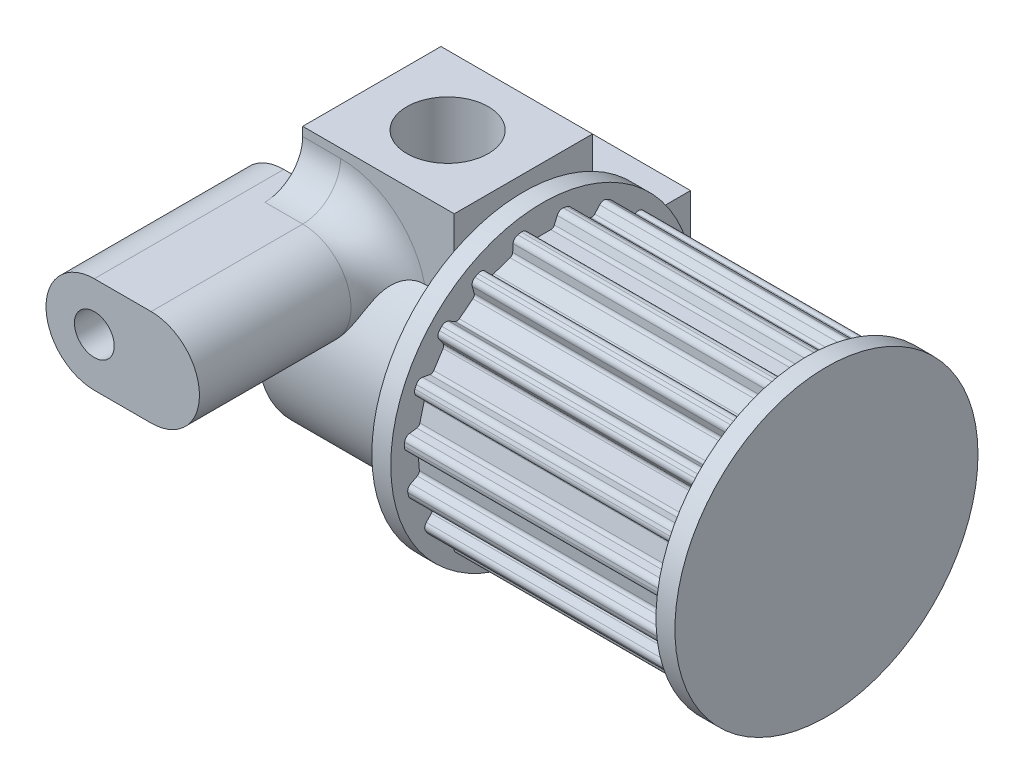
SolidWorks part; units mm, degrees
material "PLA Black"
ref_plane "Front" through (0, 0, 0) normal (0, 0, 1) x (1, 0, 0)
ref_plane "Top" through (0, 0, 0) normal (0, 1, 0) x (1, 0, 0)
ref_plane "Right" through (0, 0, 0) normal (1, 0, 0) x (0, 0, -1)
sketch "Sketch1" plane through (0, 0, 0) normal (1, 0, 0) x (0, 0, -1)
  line L0 (1.118, 1) -> (-1.118, 1) construction
  line L1 (-3.65, 4.8249) -> (3.65, 4.8249)
  line L2 (4.8249, 3.65) -> (4.8249, -3.65)
  line L3 (0, 0) -> (11.6334, 0) construction
  line L4 (0, 0) -> (0, 8.6732) construction
  arc A0 (-1.118, 1) -> (1.118, 1) centre (0, 0) ccw construction
  circle A1 centre (0, 0) radius 1.75
  arc A2 (4.8249, -3.65) -> (-3.65, 4.8249) centre (0, 0) cw
  arc A3 (4.8249, 3.65) -> (3.65, 4.8249) centre (0, 0) ccw
  dimension "D1" = 3
  dimension "D3" = 0.25
  dimension "D5" = 6.05
  dimension "D2" = 1
  dimension "D4" = 7.3
extrude "Boss-Extrude1" add sketch "Sketch1" along normal mid plane 8
sketch "Sketch2" plane through (0, 4.8249, 0) normal (0, 1, 0) x (1, 0, 0)
  circle A0 centre (0, 0) radius 2.15
  dimension "D1" = 4.3
extrude "Cut-Extrude1" cut sketch "Sketch2" against normal blind 5
sketch "Sketch7" plane through (4, 0, 0) normal (1, 0, 0) x (0, 0, -1)
  circle A0 centre (0, 0) radius 1.75 construction
  circle A1 centre (0, 0) radius 7.3
  circle A2 centre (0, 0) radius 1.75
  dimension "D1" = 14.6
extrude "Boss-Extrude5" add sketch "Sketch7" along normal blind 15
sketch "Sketch8" plane through (19, 0, 0) normal (1, 0, 0) x (0, 0, -1)
  line L0 (-0.4541, 6.5499) -> (0.4528, 6.5499)
  line L1 (0.6374, 6.6734) -> (0.7865, 7.0333)
  line L2 (-0.6389, 6.6734) -> (-0.788, 7.0333)
  line L6 (0, 9.2013) -> (0, 0) construction
  arc A0 (0.4528, 6.5499) -> (0.6374, 6.6734) centre (0.4526, 6.7499) ccw
  arc A1 (-0.4541, 6.5499) -> (-0.6389, 6.6734) centre (-0.4541, 6.7499) cw
  arc A2 (0.7865, 7.0333) -> (1.1093, 7.2152) centre (1.0638, 6.9187) cw
  arc A3 (-0.788, 7.0333) -> (-1.1108, 7.215) centre (-1.0652, 6.9185) ccw
  circle A4 centre (0, 0) radius 7.3 construction
  arc A5 (-1.1108, 7.215) -> (1.1093, 7.2152) centre (0, 0) cw
  point P3 (-0.0007, 6.5499)
  point P15 (0, 9.84)
extrude "Cut-Extrude3" cut sketch "Sketch8" against normal up to surface (15 mm away) up to face at (4, 0, -7.3)
pattern_circular "CirPattern1" count 19 over 360 about axis through (19, 0, 0) along (-1, 0, 0) of "Cut-Extrude3"
sketch "Sketch9" plane through (19, 0, 0) normal (1, 0, 0) x (0, 0, -1)
  circle A0 centre (0, 0) radius 8
  dimension "D1" = 16
extrude "Boss-Extrude6" add sketch "Sketch9" along normal blind 1
sketch "Sketch10" plane through (4, 0, 0) normal (-1, 0, 0) x (0, 0, 1)
  circle A0 centre (0, 0) radius 8
  circle A1 centre (0, 0) radius 8 construction
extrude "Boss-Extrude7" add sketch "Sketch10" against normal blind 1
sketch "Sketch3" plane through (0, 0, -4.8249) normal (0, 0, -1) x (-1, 0, 0)
  circle A0 centre (0, 0) radius 2.15
  dimension "D1" = 4.3
extrude "Cut-Extrude2" cut sketch "Sketch3" against normal blind 5
sketch "Sketch4" plane through (0, 4.8249, 0) normal (0, 1, 0) x (1, 0, 0)
  line L0 (4, 3.65) -> (-4, 3.65) construction
  line L2 (4, -3.65) -> (-4, -3.65) construction
  line L3 (-4, 3.65) -> (-4, -3.65) construction
  line L4 (4, 3.65) -> (-4, 3.65)
  line L5 (4, 3.65) -> (4, -3.65)
  line L6 (4, -3.65) -> (-4, -3.65)
  line L7 (-4, 3.65) -> (-4, -3.65)
  line L8 (4, 7.3) -> (4, -7.3) construction
  circle A0 centre (0, 0) radius 2.15 construction
  circle A1 centre (0, 0) radius 2.15
extrude "Boss-Extrude2" add sketch "Sketch4" along normal blind 4
sketch "Sketch5" plane through (0, 0, -4.8249) normal (0, 0, -1) x (-1, 0, 0)
  line L0 (-4, 3.65) -> (4, 3.65) construction
  line L1 (4, -3.65) -> (4, 3.65) construction
  line L2 (-4, -3.65) -> (4, -3.65) construction
  line L4 (-4, 3.65) -> (4, 3.65)
  line L5 (4, -3.65) -> (4, 3.65)
  line L6 (-4, -3.65) -> (4, -3.65)
  line L7 (-4, -3.65) -> (-4, 3.65)
  line L8 (-4, -7.3) -> (-4, 7.3) construction
  circle A0 centre (0, 0) radius 2.15 construction
  circle A1 centre (0, 0) radius 2.15
extrude "Boss-Extrude3" add sketch "Sketch5" along normal blind 4
ref_axis "Axis1" through (4, 0, 0) along (-1, 0, 0)
sketch "Sketch6" plane through (0, 0, 3.65) normal (0, 0, 1) x (1, 0, 0)
  line L0 (-4, 8.8249) -> (-4, 4.8249) construction
  line L2 (-2, 6.3555) -> (-5, 6.3555)
  line L3 (-5, 1.2545) -> (-2, 1.2545)
  line L6 (4, 0) -> (-4, 0) construction
  circle A0 centre (-5, 3.805) radius 1.0505
  arc A1 (-5, 6.3555) -> (-5, 1.2545) centre (-5, 3.805) ccw
  arc A2 (-2, 6.3555) -> (-2, 1.2545) centre (-2, 3.805) cw
  dimension "D1" = 2.101
  dimension "D2" = 3.805
  dimension "D3" = 1.5
  dimension "D4" = 1
  dimension "D5" = 3
extrude "Boss-Extrude4" add sketch "Sketch6" along normal blind 10
fillet "Fillet1" radius 2 2 edges at (-0.6029, 5.9388, 3.65) (-3, 6.3555, 3.65)
equation "\"knee_angle\"= 70"
equation "\"ankle_angle\" = 80"
equation "\"hip_angle\" = 40"
equation "\"spring_ankle_parallel_arm_diameter\"= 1.1"
equation "\"spring_ankle_parallel_arm_length\"= 13"
equation "\"spring_ankle_parallel_intern_diameter\"= 5.7"
equation "\"spring_ankle_parallel_angle\"= \"ankle_angle\""
equation "\"spring_ankle_parallel_turns\"= 3"
equation "\"spring_ankle_parallel_pitch\"= \"spring_ankle_parallel_arm_diameter\" * 1.01"
equation "\"spring_ankle_parallel_cutting_distance\"= (1-\"spring_ankle_parallel_angle\" / 360) * \"spring_ankle_parallel_pitch\""
equation "\"spring_ankle_serial_arm_diameter\"= 1.91"
equation "\"spring_ankle_serial_arm_length\"= 10"
equation "\"spring_ankle_serial_intern_diameter\"= 5.7"
equation "\"spring_ankle_serial_angle\"= \"90\""
equation "\"spring_ankle_serial_turns\"= 3"
equation "\"spring_ankle_serial_pitch\"= \"spring_ankle_serial_arm_diameter\" * 1.01"
equation "\"spring_ankle_serial_cutting_distance\"= (1-\"spring_ankle_serial_angle\" / 360) * \"spring_ankle_serial_pitch\""
equation "\"spring_knee_parallel_arm_diameter\"= 1.1"
equation "\"spring_knee_parallel_arm_length\"= 13"
equation "\"spring_knee_parallel_intern_diameter\"= 5.7"
equation "\"spring_knee_parallel_angle\"= -\"knee_angle\" + 90"
equation "\"spring_knee_parallel_turns\"= 3"
equation "\"spring_knee_parallel_pitch\"= \"spring_knee_parallel_arm_diameter\" * 1.01"
equation "\"spring_knee_parallel_cutting_distance\"= (1-(\"spring_knee_parallel_angle\") / 360) * \"spring_knee_parallel_pitch\""
equation "\"spring_knee_serial_arm_diameter\"= 1.91"
equation "\"spring_knee_serial_arm_length\"= 10"
equation "\"spring_knee_serial_intern_diameter\"= 5.7"
equation "\"spring_knee_serial_angle\"= \"90\""
equation "\"spring_knee_serial_turns\"= 3"
equation "\"spring_knee_serial_pitch\"= \"spring_knee_serial_arm_diameter\" * 1.01"
equation "\"spring_knee_serial_cutting_distance\"= (1-\"spring_knee_serial_angle\" / 360) * \"spring_knee_serial_pitch\""
equation "\"D2@Sketch6\" = ( \"spring_ankle_serial_intern_diameter\" + \"spring_ankle_serial_arm_diameter\" ) / 2"
equation "\"D1@Sketch6\" = \"spring_ankle_serial_arm_diameter\" * 1.1"
